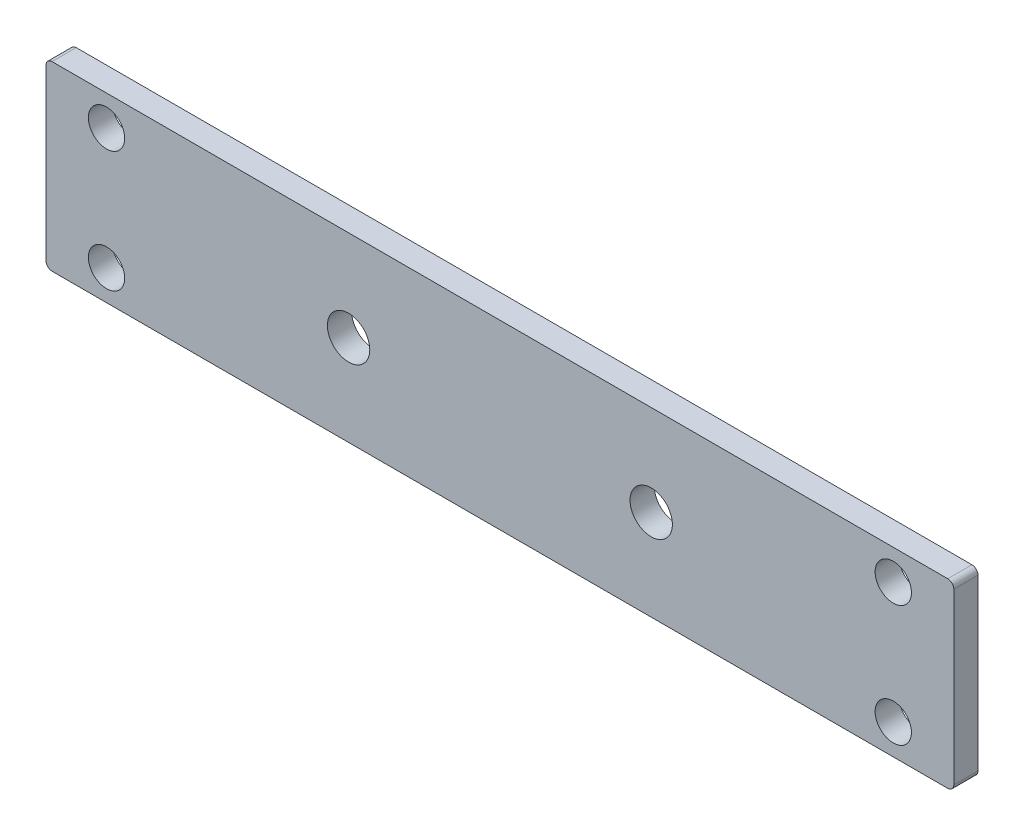
SolidWorks part; units mm, degrees
ref_plane "Front Plane" through (0, 0, 0) normal (0, 0, 1) x (1, 0, 0)
ref_plane "Top Plane" through (0, 0, 0) normal (0, 1, 0) x (1, 0, 0)
ref_plane "Right Plane" through (0, 0, 0) normal (1, 0, 0) x (0, 0, -1)
sketch "Sketch1" plane through (0, 0, 0) normal (0, 0, 1) x (1, 0, 0)
  line L0 (-99.5858, 0) -> (95.4969, 0) construction
  line L1 (-75, -15) -> (75, -15)
  line L2 (-75, -15) -> (-75, 15)
  line L3 (-75, 15) -> (75, 15)
  line L4 (75, -15) -> (75, 15)
  line L5 (0, 37.1154) -> (0, -41.7194) construction
  line L6 (-65, 37.1154) -> (-65, -41.7194) construction
  line L7 (65, 37.1154) -> (65, -41.7194) construction
  line L8 (-99.5858, -10) -> (95.4969, -10) construction
  line L9 (-99.5858, 10) -> (95.4969, 10) construction
  circle A1 centre (25, 0) radius 3.5
  circle A2 centre (-25, 0) radius 3.5
  circle A3 centre (65, -10) radius 3
  circle A4 centre (65, 10) radius 3
  circle A5 centre (-65, -10) radius 3
  circle A6 centre (-65, 10) radius 3
  dimension "D3" = 7
  dimension "D10" = 6
  dimension "D1" = 30
  dimension "D2" = 150
  dimension "D4" = 15
  dimension "D5" = 50
  dimension "D6" = 65
  dimension "D7" = 65
  dimension "D8" = 10
  dimension "D9" = 10
base flange "Base-Flange1" sketch "Sketch1" thickness 4 reverse thickness direction no parameters "D1"=0.7366
fillet "Fillet1" radius 1 4 edges at (-75, -15, -2) (75, -15, -2) (-75, 15, -2) (75, 15, -2)
sketch "Bend-Lines1" [suppressed] plane through (0, 0, 0) normal (0, 1, 0) x (1, 0, 0)
sketch "Bounding-Box1" [suppressed] plane through (0, 0, 0) normal (0, 1, 0) x (1, 0, 0)
sheet metal parameters "Sheet-Metal1" thickness 4 parameters "D1"=0.7366
flat pattern "Flat-Pattern1" [suppressed]
sketch "Bend-Lines2" plane through (0, 0, 0) normal (0, 1, 0) x (1, 0, 0)
sketch3d "Bounding-Box2" [suppressed]
  line L0 (-75, -15, 0) -> (75, -15, 0) construction
  line L1 (-75, 15, 0) -> (75, 15, 0) construction
  line L2 (-75, -15, 0) -> (-75, 15, 0) construction
  line L3 (75, -15, 0) -> (75, 15, 0) construction
